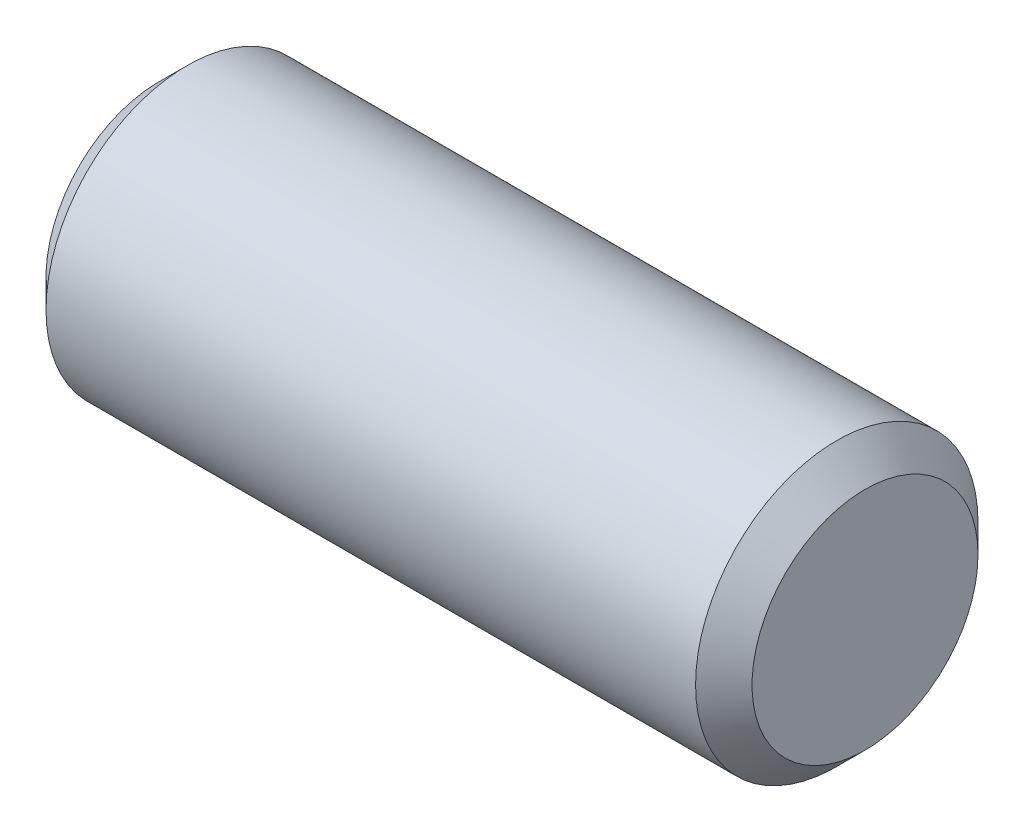
SolidWorks part; units mm, degrees
ref_plane "Front" through (0, 0, 0) normal (0, 0, 1) x (1, 0, 0)
ref_plane "Top" through (0, 0, 0) normal (0, 1, 0) x (1, 0, 0)
ref_plane "Right" through (0, 0, 0) normal (1, 0, 0) x (0, 0, -1)
sketch "Sketch1" plane through (0, 0, 0) normal (0, 0, 1) x (1, 0, 0)
  line L0 (-7.9375, 0) -> (7.9375, 0) construction
  line L1 (7.9375, 3.175) -> (7.9375, -3.175) construction
  line L2 (-7.9375, 3.175) -> (-7.9375, -3.175) construction
  dimension "Length" = 15.875
  dimension "Diameter" = 6.35
sketch "Sketch2" plane through (0, 0, 0) normal (1, 0, 0) x (0, 0, -1)
  circle A0 centre (0, 0) radius 3.175
extrude "Extrude1" add sketch "Sketch2" against normal up to vertex (7.9375 mm away) and the other way up to vertex (7.9375 mm away) up to point (-7.9375, 3.175, 0) other way up to point (7.9375, 3.175, 0)
chamfer "Chamfer1" distance 0.635 angle 45 2 edges at (7.9375, 0, -3.175) (-7.9375, 0, -3.175)
equation "\"D1@Chamfer1\" = \"Diameter@Sketch1\"*.1"
